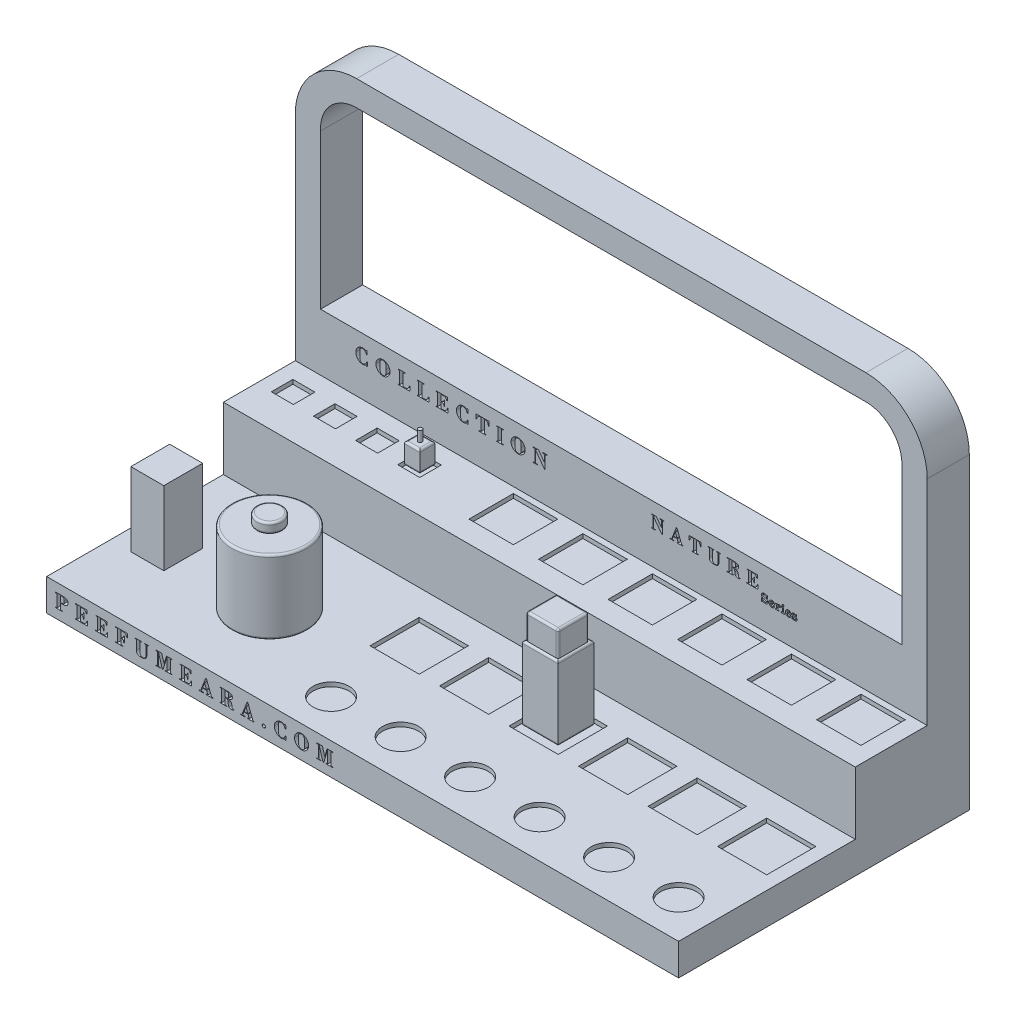
SolidWorks part; units mm, degrees
material "PVC 0.007 Plasticized"
ref_plane "Front Plane" through (0, 0, 0) normal (0, 0, 1) x (1, 0, 0)
ref_plane "Top Plane" through (0, 0, 0) normal (0, 1, 0) x (1, 0, 0)
ref_plane "Right Plane" through (0, 0, 0) normal (1, 0, 0) x (0, 0, -1)
sketch "Sketch1" plane through (0, 0, 0) normal (1, 0, 0) x (0, 0, -1)
  line L0 (0, 0) -> (83.8864, 0)
  line L1 (83.8864, 0) -> (83.8864, 29.7267)
  line L2 (83.8864, 29.7267) -> (138.0461, 29.7267)
  line L3 (138.0461, 29.7267) -> (138.0461, -15.067)
  line L4 (138.0461, -15.067) -> (0, -15.067)
  line L5 (0, -15.067) -> (0, 0)
extrude "Boss-Extrude1" add sketch "Sketch1" against normal blind 300
sketch "Sketch3" plane through (0, 0, -138.0461) normal (0, 0, -1) x (-1, 0, 0)
  line L0 (0, -15.067) -> (0, 131.1063)
  line L1 (29.1278, 160.2341) -> (270.8971, 160.2341)
  line L2 (300, 129.9017) -> (300, -15.067)
  line L3 (300, -15.067) -> (300, 29.7267) construction
  line L4 (0, -15.067) -> (300, -15.067)
  line L5 (288, 130.1827) -> (288, -3.067)
  line L6 (12, -3.067) -> (288, -3.067)
  line L7 (12, -3.067) -> (12, 131.1063)
  line L8 (29.1278, 148.2341) -> (270.8971, 148.2341)
  arc A0 (0, 131.1063) -> (29.1278, 160.2341) centre (29.1278, 131.1063) cw
  arc A1 (270.8971, 160.2341) -> (300, 129.9017) centre (270.8971, 131.1063) cw
  arc A2 (12, 131.1063) -> (29.1278, 148.2341) centre (29.1278, 131.1063) cw
  arc A3 (270.8971, 148.2341) -> (288, 130.1827) centre (270.8971, 131.1063) cw
  dimension "D1" = 12
extrude "Boss-Extrude2" add sketch "Sketch3" against normal blind 20
sketch "Sketch4" plane through (0, 0, 0) normal (0, 1, 0) x (1, 0, 0)
  circle A0 centre (-183.0872, 18.1255) radius 8.565
  circle A1 centre (-150.0872, 18.1255) radius 8.565
  circle A2 centre (-117.0872, 18.1255) radius 8.565
  circle A3 centre (-84.0872, 18.1255) radius 8.565
  circle A4 centre (-51.0872, 18.1255) radius 8.565
  circle A5 centre (-18.0872, 18.1255) radius 8.565
  dimension "D1" = 6
extrude "Cut-Extrude1" cut sketch "Sketch4" against normal blind 2
sketch "Sketch5" plane through (0, 0, 0) normal (0, 1, 0) x (1, 0, 0)
  line L0 (-183.0872, 18.1255) -> (-183.0872, 94.3097) construction
  line L1 (-138.4164, 71.6166) -> (-138.4164, 48.275)
  line L2 (-194.7579, 71.6166) -> (-171.4164, 71.6166)
  line L3 (-194.7579, 71.6166) -> (-194.7579, 48.275)
  line L4 (-194.7579, 48.275) -> (-171.4164, 48.275)
  line L5 (-171.4164, 71.6166) -> (-171.4164, 48.275)
  line L6 (-194.7579, 71.6166) -> (-171.4164, 48.275) construction
  line L7 (-194.7579, 48.275) -> (-171.4164, 71.6166) construction
  line L8 (-161.7579, 71.6166) -> (-138.4164, 71.6166)
  line L9 (-161.7579, 71.6166) -> (-161.7579, 48.275)
  line L10 (-161.7579, 48.275) -> (-138.4164, 48.275)
  line L11 (-105.4164, 71.6166) -> (-105.4164, 48.275)
  line L12 (-128.7579, 71.6166) -> (-105.4164, 71.6166)
  line L13 (-128.7579, 71.6166) -> (-128.7579, 48.275)
  line L14 (-128.7579, 48.275) -> (-105.4164, 48.275)
  line L15 (-72.4164, 71.6166) -> (-72.4164, 48.275)
  line L16 (-95.7579, 71.6166) -> (-72.4164, 71.6166)
  line L17 (-95.7579, 71.6166) -> (-95.7579, 48.275)
  line L18 (-95.7579, 48.275) -> (-72.4164, 48.275)
  line L19 (-39.4164, 71.6166) -> (-39.4164, 48.275)
  line L20 (-62.7579, 71.6166) -> (-39.4164, 71.6166)
  line L21 (-62.7579, 71.6166) -> (-62.7579, 48.275)
  line L22 (-62.7579, 48.275) -> (-39.4164, 48.275)
  line L23 (-6.4164, 71.6166) -> (-6.4164, 48.275)
  line L24 (-29.7579, 71.6166) -> (-6.4164, 71.6166)
  line L25 (-29.7579, 71.6166) -> (-29.7579, 48.275)
  line L26 (-29.7579, 48.275) -> (-6.4164, 48.275)
  point P2 (-183.0872, 59.9458)
  dimension "D1" = 6
extrude "Cut-Extrude2" cut sketch "Sketch5" against normal blind 2
sketch "Sketch7" plane through (0, 29.7267, 0) normal (0, 1, 0) x (1, 0, 0)
  line L1 (-183.0872, 48.275) -> (-183.0872, 114.3901) construction
  line L2 (-194.7579, 48.275) -> (-171.4164, 48.275) construction
  line L3 (-160.6207, 115.2021) -> (-160.6207, 94.135)
  line L4 (-193.6207, 115.2021) -> (-172.5536, 115.2021)
  line L5 (-193.6207, 115.2021) -> (-193.6207, 94.135)
  line L6 (-193.6207, 94.135) -> (-172.5536, 94.135)
  line L7 (-172.5536, 115.2021) -> (-172.5536, 94.135)
  line L8 (-193.6207, 115.2021) -> (-172.5536, 94.135) construction
  line L9 (-193.6207, 94.135) -> (-172.5536, 115.2021) construction
  line L10 (-160.6207, 94.135) -> (-139.5536, 94.135)
  line L11 (-139.5536, 115.2021) -> (-139.5536, 94.135)
  line L12 (-160.6207, 115.2021) -> (-139.5536, 115.2021)
  line L13 (-127.6207, 115.2021) -> (-127.6207, 94.135)
  line L14 (-127.6207, 94.135) -> (-106.5536, 94.135)
  line L15 (-106.5536, 115.2021) -> (-106.5536, 94.135)
  line L16 (-127.6207, 115.2021) -> (-106.5536, 115.2021)
  line L17 (-94.6207, 115.2021) -> (-94.6207, 94.135)
  line L18 (-94.6207, 94.135) -> (-73.5536, 94.135)
  line L19 (-73.5536, 115.2021) -> (-73.5536, 94.135)
  line L20 (-94.6207, 115.2021) -> (-73.5536, 115.2021)
  line L21 (-61.6207, 115.2021) -> (-61.6207, 94.135)
  line L22 (-61.6207, 94.135) -> (-40.5536, 94.135)
  line L23 (-40.5536, 115.2021) -> (-40.5536, 94.135)
  line L24 (-61.6207, 115.2021) -> (-40.5536, 115.2021)
  line L25 (-28.6207, 115.2021) -> (-28.6207, 94.135)
  line L26 (-28.6207, 94.135) -> (-7.5536, 94.135)
  line L27 (-7.5536, 115.2021) -> (-7.5536, 94.135)
  line L28 (-28.6207, 115.2021) -> (-7.5536, 115.2021)
  point P0 (-183.0872, 104.6686)
  dimension "D1" = 6
extrude "Cut-Extrude3" cut sketch "Sketch7" against normal blind 2
sketch "Sketch13" plane through (0, 0, 0) normal (0, 1, 0) x (1, 0, 0)
  circle A0 centre (-233.5807, 39.3855) radius 17.8649
extrude "Boss-Extrude4" add sketch "Sketch13" along normal blind 35 separate body
sketch "Sketch22" plane through (0, 35, 0) normal (0, 1, 0) x (1, 0, 0)
  circle A0 centre (-233.5807, 39.3855) radius 6.0878
extrude "Boss-Extrude10" add sketch "Sketch22" along normal blind 5 separate body
sketch "Sketch23" plane through (0, 0, 0) normal (0, 1, 0) x (1, 0, 0)
  line L0 (-233.5807, 39.3855) -> (-287.4979, 39.3855) construction
  line L2 (-290.2088, 48.602) -> (-274.5456, 48.602)
  line L3 (-290.2088, 48.602) -> (-290.2088, 30.1689)
  line L4 (-290.2088, 30.1689) -> (-274.5456, 30.1689)
  line L5 (-274.5456, 48.602) -> (-274.5456, 30.1689)
  line L6 (-290.2088, 48.602) -> (-274.5456, 30.1689) construction
  line L7 (-290.2088, 30.1689) -> (-274.5456, 48.602) construction
  point P2 (-282.3772, 39.3855)
extrude "Boss-Extrude11" add sketch "Sketch23" along normal blind 35 separate body
sketch "Sketch24" plane through (0, 0, 0) normal (0, 1, 0) x (1, 0, 0)
  line L1 (-125.7194, 68.5372) -> (-108.7142, 68.5372)
  line L2 (-125.7194, 68.5372) -> (-125.7194, 51.532)
  line L3 (-125.7194, 51.532) -> (-108.7142, 51.532)
  line L4 (-108.7142, 68.5372) -> (-108.7142, 51.532)
extrude "Boss-Extrude12" add sketch "Sketch24" along normal blind 35 separate body
sketch "Sketch25" plane through (0, 35, 0) normal (0, 1, 0) x (1, 0, 0)
  line L1 (-124.9462, 67.0828) -> (-109.6267, 67.0828)
  line L2 (-124.9462, 67.0828) -> (-124.9462, 52.4503)
  line L3 (-124.9462, 52.4503) -> (-109.6267, 52.4503)
  line L4 (-109.6267, 67.0828) -> (-109.6267, 52.4503)
  line L5 (-124.9462, 67.0828) -> (-109.6267, 52.4503) construction
  line L6 (-124.9462, 52.4503) -> (-109.6267, 67.0828) construction
  point P0 (-117.2864, 59.7666)
extrude "Boss-Extrude13" add sketch "Sketch25" along normal blind 12 separate body
sketch "Sketch26" plane through (0, 29.7267, 0) normal (0, 1, 0) x (1, 0, 0)
  line L0 (-193.6207, 104.6686) -> (-285.9006, 104.6686) construction
  line L1 (-193.6207, 115.2021) -> (-193.6207, 94.135) construction
  line L2 (-252.8836, 109.7797) -> (-242.4295, 99.5575) construction
  line L3 (-232.8836, 109.7797) -> (-222.4295, 109.7797)
  line L4 (-232.8836, 109.7797) -> (-232.8836, 99.5575)
  line L5 (-232.8836, 99.5575) -> (-222.4295, 99.5575)
  line L6 (-222.4295, 109.7797) -> (-222.4295, 99.5575)
  line L7 (-232.8836, 109.7797) -> (-222.4295, 99.5575) construction
  line L8 (-232.8836, 99.5575) -> (-222.4295, 109.7797) construction
  line L9 (-252.8836, 99.5575) -> (-242.4295, 109.7797) construction
  line L10 (-252.8836, 109.7797) -> (-252.8836, 99.5575)
  line L11 (-252.8836, 109.7797) -> (-242.4295, 109.7797)
  line L12 (-242.4295, 109.7797) -> (-242.4295, 99.5575)
  line L13 (-252.8836, 99.5575) -> (-242.4295, 99.5575)
  line L14 (-272.8836, 109.7797) -> (-262.4295, 99.5575) construction
  line L15 (-272.8836, 99.5575) -> (-262.4295, 109.7797) construction
  line L16 (-272.8836, 109.7797) -> (-272.8836, 99.5575)
  line L17 (-272.8836, 109.7797) -> (-262.4295, 109.7797)
  line L18 (-262.4295, 109.7797) -> (-262.4295, 99.5575)
  line L19 (-272.8836, 99.5575) -> (-262.4295, 99.5575)
  line L20 (-292.8836, 109.7797) -> (-282.4295, 99.5575) construction
  line L21 (-292.8836, 99.5575) -> (-282.4295, 109.7797) construction
  line L22 (-292.8836, 109.7797) -> (-292.8836, 99.5575)
  line L23 (-292.8836, 109.7797) -> (-282.4295, 109.7797)
  line L24 (-282.4295, 109.7797) -> (-282.4295, 99.5575)
  line L25 (-292.8836, 99.5575) -> (-282.4295, 99.5575)
  point P4 (-227.6565, 104.6686)
  point P10 (-247.6565, 104.6686)
  point P15 (-267.6565, 104.6686)
  point P20 (-287.6565, 104.6686)
  dimension "D1" = 4
extrude "Cut-Extrude4" cut sketch "Sketch26" against normal blind 2
sketch "Sketch29" plane through (0, 29.7267, 0) normal (0, 1, 0) x (1, 0, 0)
  line L1 (-231.0633, 107.969) -> (-223.6596, 107.969)
  line L2 (-231.0633, 107.969) -> (-231.0633, 100.833)
  line L3 (-231.0633, 100.833) -> (-223.6596, 100.833)
  line L4 (-223.6596, 107.969) -> (-223.6596, 100.833)
extrude "Boss-Extrude15" add sketch "Sketch29" along normal blind 10 separate body
sketch "Sketch30" plane through (0, 39.7267, 0) normal (0, 1, 0) x (1, 0, 0)
  circle A0 centre (-227.3216, 104.6479) radius 0.9421
extrude "Boss-Extrude16" add sketch "Sketch30" along normal blind 5 separate body
fillet "Fillet1" radius 1 8 edges at (-227.3614, 29.7267, -100.833) (-223.6596, 29.7267, -104.401) (-227.3614, 29.7267, -107.969) (-231.0633, 29.7267, -104.401) (-231.0633, 39.7267, -104.401) (-227.3614, 39.7267, -107.969) (-223.6596, 39.7267, -104.401) (-227.3614, 39.7267, -100.833)
fillet "Fillet2" radius 1 8 edges at (-117.2168, 0, -68.5372) (-108.7142, 0, -60.0346) (-125.7194, 0, -60.0346) (-117.2168, 0, -51.532) (-117.2168, 35, -68.5372) (-125.7194, 35, -60.0346) (-117.2168, 35, -51.532) (-108.7142, 35, -60.0346)
fillet "Fillet3" radius 1 2 edges at (-233.5807, 0, -21.5205) (-233.5807, 35, -21.5205)
fillet "Fillet4" radius 1 2 edges at (-233.5807, 35, -33.2976) (-233.5807, 40, -33.2976)
fillet "Fillet5" radius 1 4 edges at (-124.9462, 41, -52.4503) (-124.9462, 41, -67.0828) (-109.6267, 41, -67.0828) (-109.6267, 41, -52.4503)
fillet "Fillet6" radius 1 8 edges at (-109.9196, 47, -66.7899) (-109.6267, 47, -59.7666) (-109.9196, 47, -52.7432) (-117.2864, 47, -52.4503) (-124.6533, 47, -52.7432) (-124.9462, 47, -59.7666) (-124.6533, 47, -66.7899) (-117.2864, 47, -67.0828)
sketch "Sketch32" plane through (0, 0, 0) normal (0, 0, 1) x (1, 0, 0)
  text T0 "P E E F U M E A R A . C O M" font "Bodoni Bd BT" height in points 24
extrude "Cut-Extrude5" cut sketch "Sketch32" against normal blind 2
sketch "Sketch34" plane through (0, 0, -138.0461) normal (0, 0, -1) x (-1, 0, 0)
  line L0 (288, 29.7267) -> (288, 130.1827) construction
  line L1 (12, 29.7267) -> (288, 29.7267)
  line L2 (12, 29.7267) -> (12, 56.8918)
  line L3 (12, 56.8918) -> (288, 56.8918)
  line L4 (288, 29.7267) -> (288, 56.8918)
extrude "Boss-Extrude17" add sketch "Sketch34" against normal up to surface (20 mm away) up to face at (-150.0682, 106.4669, -118.0461)
sketch "Sketch36" plane through (0, 0, -118.0461) normal (0, 0, 1) x (1, 0, 0)
  text T0 "Series" font "Clarendon BT" height in points 14
extrude "Cut-Extrude7" cut sketch "Sketch36" against normal blind 2
sketch "Sketch35" plane through (0, 0, -118.0461) normal (0, 0, 1) x (1, 0, 0)
  text T0 "N A T U R E" font "Bodoni Bd BT" height in points 22
extrude "Cut-Extrude8" cut sketch "Sketch35" against normal blind 2
sketch "Sketch38" plane through (0, 0, -118.0461) normal (0, 0, 1) x (1, 0, 0)
  text T0 "C O L L E C T I O N" font "Bodoni Bd BT" height in points 24
extrude "Cut-Extrude12" cut sketch "Sketch38" against normal blind 2
